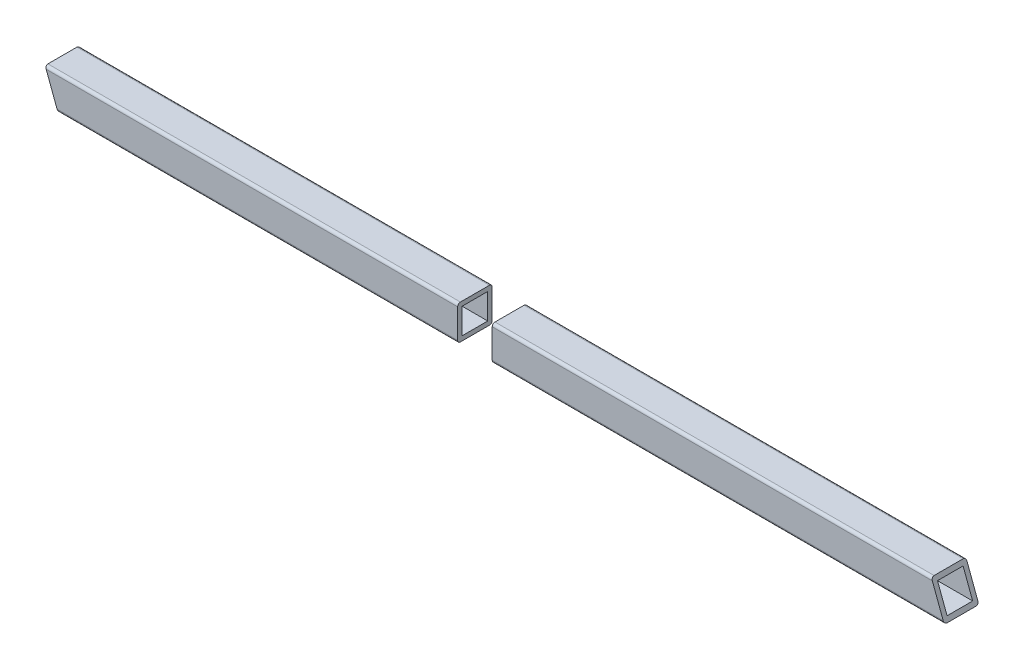
SolidWorks part; units mm, degrees
material "Plain Carbon Steel"
ref_plane "Front Plane" through (0, 0, 0) normal (0, 0, 1) x (1, 0, 0)
ref_plane "Top Plane" through (0, 0, 0) normal (0, 1, 0) x (1, 0, 0)
ref_plane "Right Plane" through (0, 0, 0) normal (1, 0, 0) x (0, 0, -1)
sketch "Sketch1" plane through (0, 0, 0) normal (1, 0, 0) x (0, 0, -1)
  line L0 (0, 2.54) -> (0, 29.21)
  line L1 (-2.54, 31.75) -> (-29.21, 31.75)
  line L2 (-31.75, 29.21) -> (-31.75, 2.54)
  line L3 (-29.21, 0) -> (-2.54, 0)
  line L4 (-4.1275, 4.1275) -> (-4.1275, 27.6225)
  line L5 (-4.1275, 27.6225) -> (-27.6225, 27.6225)
  line L6 (-27.6225, 27.6225) -> (-27.6225, 4.1275)
  line L7 (-27.6225, 4.1275) -> (-4.1275, 4.1275)
  arc A0 (-31.75, 2.54) -> (-29.21, 0) centre (-29.21, 2.54) ccw
  arc A1 (0, 2.54) -> (-2.54, 0) centre (-2.54, 2.54) cw
  arc A2 (0, 29.21) -> (-2.54, 31.75) centre (-2.54, 29.21) ccw
  arc A3 (-31.75, 29.21) -> (-29.21, 31.75) centre (-29.21, 29.21) cw
  arc A4 (-4.1275, 27.6225) -> (-4.1275, 27.6225) centre (-4.1275, 27.6225) ccw
  arc A5 (-27.6225, 27.6225) -> (-27.6225, 27.6225) centre (-27.6225, 27.6225) cw
  arc A6 (-27.6225, 4.1275) -> (-27.6225, 4.1275) centre (-27.6225, 4.1275) ccw
  arc A7 (-4.1275, 4.1275) -> (-4.1275, 4.1275) centre (-4.1275, 4.1275) cw
  point P12 (0, 0)
  point P15 (0, 31.75)
  point P18 (-31.75, 31.75)
  dimension "D3" = 2.54
  dimension "D1" = 31.75
  dimension "D2" = 31.75
  dimension "D4" = 4.1275
extrude "Boss-Extrude1" add sketch "Sketch1" along normal blind 393.7
scale "Scale1" scale about centroid uniform scaling no x scale factor 1 y scale factor 0.4 z scale factor 0.4
sketch "Sketch4" plane through (0, 0, 9.525) normal (0, 0, -1) x (-1, 0, 0)
  line L0 (-393.7, 15.875) -> (0, 15.875) construction
  line L1 (-393.7, 10.541) -> (-393.7, 21.209) construction
  line L2 (0, 10.541) -> (0, 21.209) construction
sketch "Sketch5" plane through (0, 0, 9.525) normal (0, 0, -1) x (-1, 0, 0)
  line L0 (-164.1615, 9.525) -> (-151.4615, 9.525)
  line L1 (-164.1615, 306.0436) -> (-164.1615, -310.468) construction
  line L2 (-393.7, 9.525) -> (0, 9.525) construction
  line L3 (-151.4615, 295.0088) -> (-151.4615, -310.468) construction
  line L4 (-151.4615, 9.525) -> (-151.4615, 22.225)
  line L5 (-393.7, 22.225) -> (0, 22.225) construction
  line L6 (-151.4615, 22.225) -> (-164.1615, 22.225)
  line L7 (-164.1615, 22.225) -> (-164.1615, 9.525)
  line L12 (0, 22.225) -> (-4.7467, 9.525)
  line L13 (44.5784, 141.497) -> (-129.0921, -323.168) construction
  line L14 (-4.7467, 9.525) -> (0, 9.525)
  line L15 (0, 9.525) -> (0, 22.225)
  line L16 (-330.1401, 9.525) -> (-325.3934, 22.225)
  line L17 (-454.4855, -323.168) -> (-201.048, 354.918) construction
  line L18 (-325.3934, 22.225) -> (-353.7525, 22.225)
  line L19 (-353.7525, 22.225) -> (-358.4992, 9.525)
  line L20 (-358.4992, 9.525) -> (-330.1401, 9.525)
extrude "Cut-Extrude3" cut sketch "Sketch5" against normal through all body kept at (164.1615, 21.209, 9.525) body kept at (0.3797, 21.209, 9.525)
